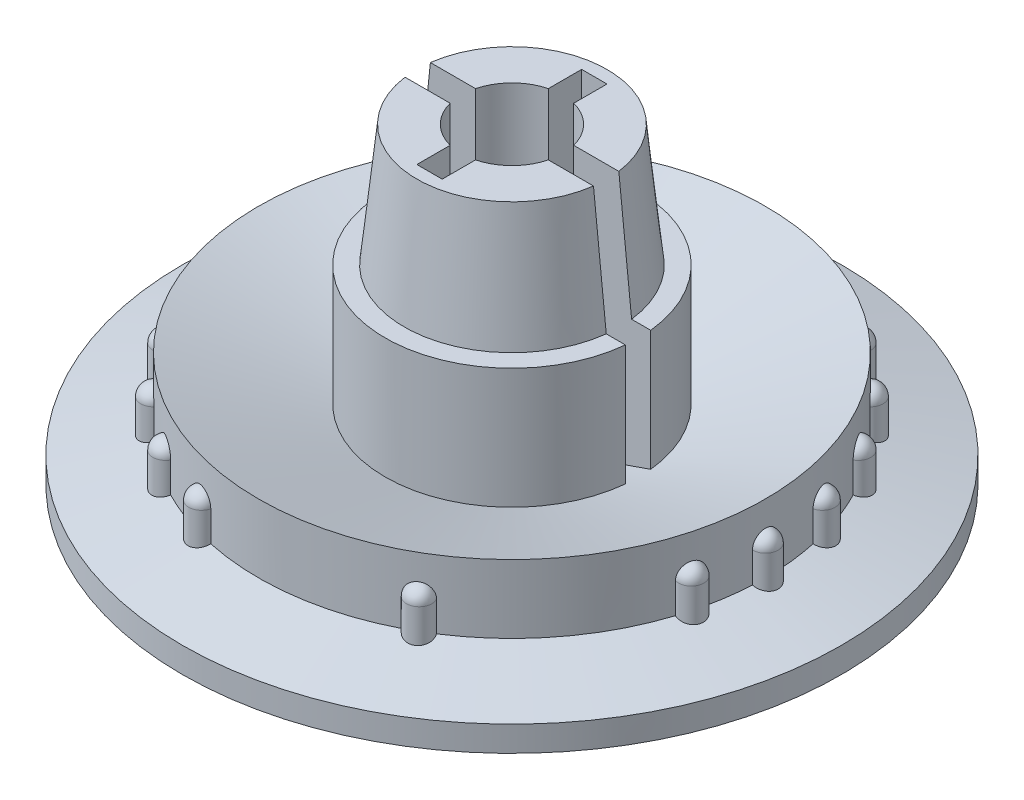
SolidWorks part; units mm, degrees
ref_plane "前视基准面" through (0, 0, 0) normal (0, 0, 1) x (1, 0, 0)
ref_plane "上视基准面" through (0, 0, 0) normal (0, 1, 0) x (1, 0, 0)
ref_plane "右视基准面" through (0, 0, 0) normal (1, 0, 0) x (0, 0, -1)
sketch "草图1" plane through (0, 0, 0) normal (0, 1, 0) x (1, 0, 0)
  circle A0 centre (0, 0) radius 13
extrude "凸台-拉伸1" add sketch "草图1" along normal blind 2
sketch "草图2" plane through (0, 2, 0) normal (0, 1, 0) x (1, 0, 0)
  circle A0 centre (0, 0) radius 10
extrude "凸台-拉伸2" add sketch "草图2" along normal blind 2.5
sketch "草图3" plane through (0, 0, 0) normal (0, 0, 1) x (1, 0, 0)
  line L0 (0, 4.5) -> (0, 1)
  line L3 (10, 4.5) -> (-10, 4.5) construction
  line L4 (0, 1) -> (10, 4.5)
  line L5 (10, 4.5) -> (0, 4.5)
revolve "切除-旋转1" cut sketch "草图3" angle 360 about L0
sketch "草图4" plane through (0, 0, 0) normal (0, 0, 1) x (1, 0, 0)
  line L0 (0, 0) -> (5, 0)
  line L1 (-13, 0) -> (13, 0) construction
  line L2 (5, 0) -> (5, 7.5)
  line L3 (4.25, 7.5) -> (5, 7.5)
  line L4 (0, 12.3) -> (3.75, 12.3)
  line L5 (3.75, 12.3) -> (4.25, 7.5)
  line L6 (0, 12.3) -> (0, 0)
revolve "旋转1" add sketch "草图4" angle 360 about L6
sketch "草图5" plane through (0, 12.3, 0) normal (0, 1, 0) x (1, 0, 0)
  line L0 (-0.5, -1.9365) -> (-0.5, -3.25)
  line L1 (-0.5, 3.25) -> (0.5, 3.25)
  line L2 (-0.5, 3.25) -> (-0.5, 1.9365)
  line L3 (-0.5, -3.25) -> (0.5, -3.25)
  line L4 (0.5, 3.25) -> (0.5, 1.9365)
  line L5 (0.5, -1.9365) -> (0.5, -3.25)
  arc A0 (-0.5, 1.9365) -> (-0.5, -1.9365) centre (0, 0) ccw
  arc A1 (0.5, -1.9365) -> (0.5, 1.9365) centre (0, 0) ccw
extrude "切除-拉伸1" cut sketch "草图5" against normal blind 12
sketch "草图6" plane through (0, 0, 0) normal (0, -1, 0) x (-1, 0, 0)
  circle A0 centre (0, 0) radius 2
extrude "切除-拉伸2" cut sketch "草图6" against normal up to next
sketch "草图7" plane through (0, 12.3, 0) normal (0, 1, 0) x (1, 0, 0)
  line L1 (-4.9749, 0.5) -> (4.9749, 0.5)
  line L3 (-4.9749, -0.5) -> (4.9749, -0.5)
  arc A1 (-4.9749, 0.5) -> (-4.9749, -0.5) centre (0, 0) ccw
  arc A2 (4.9749, -0.5) -> (4.9749, 0.5) centre (0, 0) ccw
extrude "切除-拉伸3" cut sketch "草图7" against normal up to surface (9.55 mm away) up to face at (0, 4.5, 10)
chamfer "倒角1" distance 1 angle 75 1 edges at (0, 2, 13) first distance on face at (0, 2, 13)
sketch "草图8" plane through (0, 0, 0) normal (0, 1, 0) x (1, 0, 0)
  arc A0 (0.4998, 9.9875) -> (-0.4998, 9.9875) centre (0, 10) ccw
  circle A1 centre (0, 0) radius 10 construction
  circle A2 centre (0, 0) radius 10 construction
  arc A3 (0.4998, 9.9875) -> (-0.4998, 9.9875) centre (0, 0) ccw
extrude "凸台-拉伸3" add sketch "草图8" along normal blind 3
sketch "草图9" plane through (0, 0, 0) normal (1, 0, 0) x (0, 0, -1)
  line L0 (10, 3.5) -> (10, 3)
  line L1 (10, 3) -> (10.5, 3)
  arc A0 (10.5, 3) -> (10, 3.5) centre (10, 3) ccw
revolve "旋转2" add sketch "草图9" angle 360 about L0
pattern_circular "阵列(圆周)3" count 24 over 360 about axis through (0, 12.3, 0) along (0, 1, 0) of "旋转2", "凸台-拉伸3"
ref_plane "基准面2" through (0, 0, 0) normal (0.7071, 0, -0.7071) x (-0.7071, 0, -0.7071)
sketch "草图11" plane through (0, 0, 0) normal (0.7071, 0, -0.7071) x (-0.7071, 0, -0.7071)
  line L0 (-10, 4.5) -> (-10, 1.8038)
  line L1 (-13, 1) -> (-10, 1.8038)
  line L3 (-10, 4.5) -> (-13, 1)
  line L4 (0, -1.0106) -> (0, 4.9685) construction
  line L5 (10, 4.5) -> (13, 1)
  line L6 (13, 1) -> (10, 1.8038)
  line L7 (10, 4.5) -> (10, 1.8038)
revolve "切除-旋转3" cut sketch "草图11" angle 20 about L4 other way angle 5
sketch "草图12" plane through (0, 0, 0) normal (1, 0, 0) x (0, 0, -1)
  line L0 (-10, 4.5) -> (-10, 1.8038)
  line L1 (-13, 1) -> (-10, 1.8038)
  line L3 (-10, 4.5) -> (-13, 1)
  line L4 (0, -0.795) -> (0, 4.9925) construction
  line L5 (10, 4.5) -> (13, 1)
  line L6 (13, 1) -> (10, 1.8038)
  line L7 (10, 4.5) -> (10, 1.8038)
revolve "切除-旋转4" cut sketch "草图12" angle 20 about L4 other way angle 5
